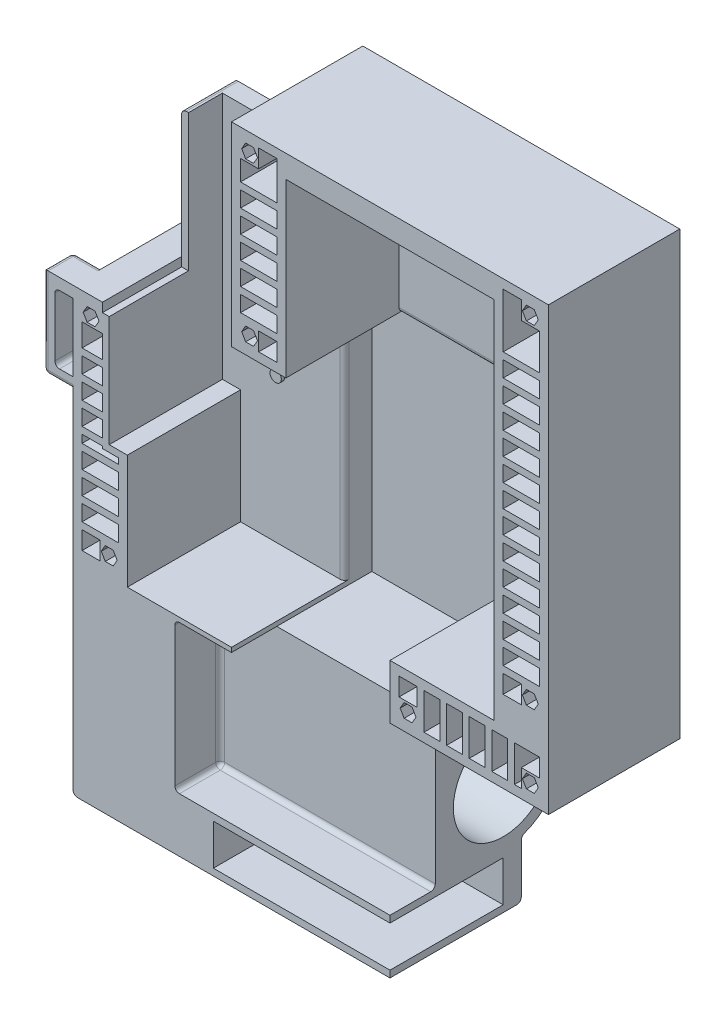
SolidWorks part; units mm, degrees
note: The reader was unsure of these and kept them because the rebuilt part matched: shared geometry of "스케치13<4>", "스케치19<3>", "스케치23<3>".
ref_plane "정면" through (0, 0, 0) normal (0, 0, 1) x (1, 0, 0)
ref_plane "윗면" through (0, 0, 0) normal (0, 1, 0) x (1, 0, 0)
ref_plane "우측면" through (0, 0, 0) normal (1, 0, 0) x (0, 0, -1)
sketch "스케치1" plane through (0, 0, 0) normal (0, 0, 1) x (1, 0, 0)
  line L21 (0, 0) -> (140, 0)
  line L22 (0, 0) -> (0, 195)
  line L23 (0, 195) -> (70, 195)
  line L24 (140, 0) -> (140, 97.5)
  line L25 (140, 97.5) -> (210, 97.5)
  line L26 (70, 195) -> (70, 292.5)
  line L27 (70, 292.5) -> (210, 292.5)
  line L28 (210, 97.5) -> (210, 292.5)
  dimension "D1" = 140
  dimension "D2" = 195
  dimension "D3" = 97.5
  dimension "D4" = 70
  dimension "D5" = 97.5
  dimension "D6" = 70
  dimension "D7" = 195
  dimension "D8" = 140
  dimension "D9" = 140
extrude "보스-돌출1" add sketch "스케치1" along normal blind 8
sketch "스케치6" plane through (0, 0, 8) normal (0, 0, 1) x (1, 0, 0)
  line L0 (140, 0) -> (140, 97.5) construction
  line L1 (0, 0) -> (140, 0)
  line L2 (0, 0) -> (0, 24)
  line L3 (0, 24) -> (140, 24)
  line L4 (140, 0) -> (140, 24)
  line L5 (210, 97.5) -> (210, 292.5) construction
  line L6 (70, 195) -> (94, 195)
  line L7 (70, 195) -> (70, 292.5)
  line L9 (94, 195) -> (94, 282.5)
  line L10 (210, 292.5) -> (70, 292.5) construction
  line L11 (70, 292.5) -> (210, 292.5)
  line L13 (94, 282.5) -> (186, 282.5)
  line L15 (140, 97.5) -> (210, 97.5) construction
  line L17 (210, 292.5) -> (210, 129.5)
  line L18 (210, 97.5) -> (202, 97.5)
  line L19 (186, 282.5) -> (186, 129.5)
  line L20 (210, 121.5) -> (210, 97.5)
  line L21 (210, 97.5) -> (140, 97.5)
  line L23 (186, 121.5) -> (140, 121.5)
  line L24 (140, 97.5) -> (140, 121.5)
  line L25 (0, 195) -> (24, 195)
  line L26 (0, 195) -> (0, 24)
  line L27 (0, 24) -> (24, 24)
  line L28 (24, 195) -> (24, 24)
  line L29 (186, 121.5) -> (210, 121.5)
  line L31 (186, 129.5) -> (210, 129.5)
  line L33 (24, 195) -> (13, 195)
  line L34 (24, 195) -> (24, 139)
  line L35 (24, 139) -> (13, 139)
  line L36 (13, 195) -> (13, 139)
  line M7 (0, 195) -> (0, 0)
  line M8 (0, 0) -> (140, 0)
  line M9 (140, 0) -> (140, 97.5)
  line M10 (140, 97.5) -> (210, 97.5)
  line M11 (210, 97.5) -> (210, 292.5)
  line M12 (210, 292.5) -> (70, 292.5)
  line M13 (70, 292.5) -> (70, 195)
  line M14 (70, 195) -> (0, 195)
  dimension "D1" = 24
  dimension "D2" = 56
  dimension "D3" = 24
  dimension "D4" = 24
  dimension "D5" = 8
  dimension "D6" = 8
  dimension "D7" = 10
  dimension "D8" = 24
  dimension "D9" = 11
  dimension "D10" = 24
extrude "보스-돌출3" add sketch "스케치6" along normal blind 50 contours L28 L27 M14 M7 | L3 M7 M8 M9 | L29 L23 L24 M10 M11 | L19 L31 L6 L9 L13 M11 M12 M13
sketch "스케치8" plane through (0, 0, 0) normal (-1, 0, 0) x (0, 0, 1)
  line L1 (58, 0) -> (0, 0) construction
  circle A0 centre (8, 51) radius 27
  dimension "D1" = 51
  dimension "D2" = 54
extrude "보스-돌출4" add sketch "스케치8" against normal blind 140
sketch "스케치9" plane through (0, 0, 0) normal (-1, 0, 0) x (0, 0, 1)
  circle A0 centre (8, 51) radius 36.5
  dimension "D1" = 73
extrude "컷-돌출1" cut sketch "스케치9" against normal blind 42
ref_plane "평면3" through (0, 0, 38) normal (0, 0, -1) x (-1, 0, 0)
sketch "스케치11" plane through (0, 0, 38) normal (0, 0, -1) x (-1, 0, 0)
  line L0 (-140, 78) -> (-140, 97.5) construction
  line L1 (-42, 24) -> (-140, 24)
  line L2 (-42, 24) -> (-42, 91.5)
  line L3 (-42, 91.5) -> (-140, 91.5)
  line L4 (-140, 24) -> (-140, 91.5)
  dimension "D1" = 67.5
sketch "스케치13" plane through (42, 0, 0) normal (-1, 0, 0) x (0, 0, 1)
  circle A0 centre (8, 51) radius 22
  dimension "D1" = 44
extrude "컷-돌출2" cut sketch "스케치13" against normal blind 80 contours A0
extrude "보스-돌출6" add sketch "스케치11" along normal blind 30
extrude "컷-돌출4" cut sketch "스케치13<4>" against normal blind 80
sketch "스케치13<4>" plane through (42, 0, 0) normal (-1, 0, 0) x (0, 0, 1) same geometry as "스케치13"
sketch "스케치14" plane through (0, 0, 38) normal (0, 0, 1) x (1, 0, 0)
  line L1 (42, 91.5) -> (140, 91.5)
  line L2 (42, 91.5) -> (42, 89.5)
  line L3 (42, 89.5) -> (140, 89.5)
  line L4 (140, 91.5) -> (140, 89.5)
  line L9 (42, 91.5) -> (140, 91.5) construction
  dimension "D2" = 2
extrude "보스-돌출7" add sketch "스케치14" along normal blind 20
sketch "스케치15" plane through (24, 0, 0) normal (1, 0, 0) x (0, 0, -1)
  line L0 (-58, 24) -> (-58, 91.5)
  line L1 (-58, 91.5) -> (-8, 91.5)
  line L2 (-8, 91.5) -> (-8, 87.5)
  line L3 (-8, 139) -> (-8, 87.5) construction
  line L4 (-8, 14.5) -> (-58, 14.5)
  line L5 (-58, 0) -> (-58, 24) construction
  line L6 (-58, 14.5) -> (-58, 24)
  arc A0 (-8, 87.5) -> (-32.5611, 24) centre (-8, 51) ccw construction
  arc A1 (-8, 87.5) -> (-8, 14.5) centre (-8, 51) ccw
  arc A2 (0, 86.6125) -> (0, 15.3875) centre (-8, 51) ccw construction
  arc A3 (-32.5611, 24) -> (0, 15.3875) centre (-8, 51) ccw construction
extrude "보스-돌출9" add sketch "스케치15" along normal up to vertex (18 mm away)
sketch "스케치17" plane through (140, 0, 0) normal (1, 0, 0) x (0, 0, -1)
  line L0 (-58, 0) -> (0, 0) construction
  line L1 (-58, 21) -> (-8, 21)
  line L2 (-58, 21) -> (-58, 3)
  line L3 (-58, 3) -> (-8, 3)
  line L4 (-8, 21) -> (-8, 3)
  line L5 (0, 0) -> (0, 25.2124) construction
  dimension "D1" = 50
  dimension "D2" = 18
  dimension "D3" = 3
  dimension "D4" = 8
extrude "컷-돌출5" cut sketch "스케치17" against normal blind 78
sketch "스케치18" plane through (0, 0, 8) normal (0, 0, 1) x (1, 0, 0)
  line L0 (70, 195) -> (13, 195) construction
  line L1 (16, 91.5) -> (70, 91.5)
  line L2 (16, 91.5) -> (16, 251.5)
  line L3 (16, 251.5) -> (70, 251.5)
  line L4 (70, 91.5) -> (70, 251.5)
  line L5 (24, 91.5) -> (140, 91.5) construction
  line L6 (70, 292.5) -> (70, 195) construction
  dimension "D1" = 56.5
  dimension "D2" = 54
extrude "보스-돌출10" add sketch "스케치18" against normal blind 8
sketch "스케치19" plane through (0, 0, 8) normal (0, 0, 1) x (1, 0, 0)
  line L1 (16, 251.5) -> (13, 251.5)
  line L2 (16, 251.5) -> (16, 139)
  line L3 (16, 139) -> (13, 139)
  line L4 (13, 251.5) -> (13, 139)
  line L5 (24, 139) -> (13, 139) construction
  dimension "D1" = 3
extrude "보스-돌출11" add sketch "스케치19" against normal blind 8
extrude "보스-돌출12" add sketch "스케치19<3>" along normal blind 15
sketch "스케치19<3>" plane through (0, 0, 8) normal (0, 0, 1) x (1, 0, 0) same geometry as "스케치19"
sketch "스케치22" plane through (0, 0, 8) normal (0, 0, 1) x (1, 0, 0)
  line L1 (70, 89.5) -> (140, 89.5)
  line L2 (70, 89.5) -> (70, 206.5)
  line L3 (70, 206.5) -> (140, 206.5)
  line L4 (140, 89.5) -> (140, 206.5)
extrude "보스-돌출14" add sketch "스케치22" along normal mid plane 40 contours L4 L3 L2 L1
sketch "스케치23" plane through (0, 0, 0) normal (0, 0, -1) x (-1, 0, 0)
  line L1 (-140, 206.5) -> (-70, 206.5)
  line L2 (-140, 206.5) -> (-140, 89.5)
  line L3 (-140, 89.5) -> (-70, 89.5)
  line L4 (-70, 206.5) -> (-70, 89.5)
extrude "컷-돌출6" cut sketch "스케치23" against normal through all
extrude "컷-돌출8" cut sketch "스케치23<3>" along normal blind 4
sketch "스케치23<3>" plane through (0, 0, 0) normal (0, 0, -1) x (-1, 0, 0) same geometry as "스케치23"
sketch "스케치26" plane through (0, 0, -12) normal (0, 0, -1) x (-1, 0, 0)
  line L1 (-140, 97.5) -> (-148, 97.5)
  line L2 (-140, 97.5) -> (-140, 206.5)
  line L3 (-140, 206.5) -> (-148, 206.5)
  line L4 (-148, 97.5) -> (-148, 206.5)
  line L5 (-148, 206.5) -> (-62, 206.5)
  line L6 (-148, 206.5) -> (-148, 214.5)
  line L7 (-148, 214.5) -> (-62, 214.5)
  line L8 (-62, 206.5) -> (-62, 214.5)
  line L9 (-62, 206.5) -> (-70, 206.5)
  line L10 (-62, 206.5) -> (-62, 89.5)
  line L11 (-62, 89.5) -> (-70, 89.5)
  line L12 (-70, 206.5) -> (-70, 89.5)
  line L13 (-140, 89.5) -> (-62, 89.5)
  line L14 (-140, 89.5) -> (-140, 81.5)
  line L15 (-140, 81.5) -> (-62, 81.5)
  line L16 (-62, 89.5) -> (-62, 81.5)
  line M10 (-140, 89.5) -> (-70, 89.5)
  line M11 (-70, 89.5) -> (-70, 206.5)
  line M12 (-70, 206.5) -> (-140, 206.5)
  line M13 (-140, 206.5) -> (-140, 89.5)
  dimension "D1" = 8
  dimension "D2" = 8
extrude "보스-돌출16" add sketch "스케치26" against normal blind 12 contours L5 L8 L7 L6 L3 M12 | L11 L10 L5 M11 | L4 L1 L3 M13 | L16 L11 L14 L15 M10
sketch "스케치30" plane through (0, 0, 8) normal (0, 0, 1) x (1, 0, 0)
  line L0 (13, 195) -> (0, 195) construction
  line L1 (6.7273, 195) -> (13.8607, 195)
  line L5 (70, 206.5) -> (94, 206.5) construction
  line L10 (74, 210.5) -> (90, 210.5)
  line L11 (74, 210.5) -> (74, 288.5)
  line L12 (74, 288.5) -> (90, 288.5)
  line L13 (90, 210.5) -> (90, 288.5)
  line L14 (190, 288.5) -> (206, 288.5)
  line L17 (206, 288.5) -> (206, 272.5)
  line L19 (206, 272.5) -> (206, 133.5)
  line L20 (206, 133.5) -> (190, 133.5)
  line L21 (190, 288.5) -> (190, 133.5)
  line L22 (94, 206.5) -> (94, 282.5) construction
  line L23 (70, 292.5) -> (70, 206.5) construction
  line L24 (210, 292.5) -> (70, 292.5) construction
  line L27 (210, 129.5) -> (210, 292.5) construction
  line L28 (186, 129.5) -> (210, 129.5) construction
  line L29 (24, 91.5) -> (70, 91.5) construction
  line L30 (144, 117.5) -> (206, 117.5)
  line L31 (144, 117.5) -> (144, 101.5)
  line L32 (144, 101.5) -> (206, 101.5)
  line L33 (206, 117.5) -> (206, 101.5)
  line L38 (4, 191) -> (20, 191)
  line L39 (4, 191) -> (4, 95.5)
  line L40 (4, 95.5) -> (20, 95.5)
  line L41 (20, 191) -> (20, 95.5)
  line L42 (0, 195) -> (0, 0) construction
  line L43 (24, 139) -> (24, 91.5) construction
  line L47 (210, 97.5) -> (210, 121.5) construction
  line L48 (140, 121.5) -> (210, 121.5) construction
  line L49 (140, 97.5) -> (210, 97.5) construction
  line L50 (140, 97.5) -> (140, 121.5) construction
  point P22 (0, 0)
  point P23 (0, 0)
  point P24 (0, 0)
  point P25 (0, 0)
  point P34 (0, 0)
  point P42 (12, 95.5)
  dimension "D1" = 4
  dimension "D2" = 4
  dimension "D3" = 4
  dimension "D4" = 4
  dimension "D7" = 4
  dimension "D8" = 4
  dimension "D9" = 4
  dimension "D10" = 4
  dimension "D11" = 4
  dimension "D12" = 4
  dimension "D17" = 4
  dimension "D18" = 4
  dimension "D19" = 4
  dimension "D20" = 4
extrude "컷-돌출10" cut sketch "스케치30" along normal through all
sketch "스케치31" plane through (0, 0, 8) normal (0, 0, 1) x (1, 0, 0)
  line L0 (206, 141.5) -> (198, 141.5)
  line L1 (206, 288.5) -> (198, 288.5)
  line L2 (206, 288.5) -> (206, 280.5)
  line L3 (206, 280.5) -> (198, 280.5)
  line L4 (198, 288.5) -> (198, 280.5)
  line L5 (200.25, 287.5322) -> (198.5, 284.5011)
  line L6 (198.5, 284.5011) -> (200.25, 281.47)
  line L7 (200.25, 281.47) -> (203.75, 281.47)
  line L8 (203.75, 281.47) -> (205.5, 284.5011)
  line L9 (205.5, 284.5011) -> (203.75, 287.5322)
  line L10 (203.75, 287.5322) -> (200.25, 287.5322)
  line L11 (206, 141.5) -> (206, 133.5)
  line L12 (206, 133.5) -> (198, 133.5)
  line L13 (198, 141.5) -> (198, 133.5)
  line L20 (206, 109.5) -> (198, 109.5)
  line L21 (206, 109.5) -> (206, 101.5)
  line L22 (206, 101.5) -> (198, 101.5)
  line L23 (198, 109.5) -> (198, 101.5)
  line L30 (152, 109.5) -> (144, 109.5)
  line L31 (152, 109.5) -> (152, 101.5)
  line L32 (152, 101.5) -> (144, 101.5)
  line L33 (144, 109.5) -> (144, 101.5)
  line L40 (82, 218.5) -> (74, 218.5)
  line L41 (82, 218.5) -> (82, 210.5)
  line L42 (82, 210.5) -> (74, 210.5)
  line L43 (74, 218.5) -> (74, 210.5)
  line L50 (82, 288.5) -> (74, 288.5)
  line L51 (82, 288.5) -> (82, 280.5)
  line L52 (82, 280.5) -> (74, 280.5)
  line L53 (74, 288.5) -> (74, 280.5)
  line L54 (76.25, 287.5322) -> (74.5, 284.5011)
  line L55 (74.5, 284.5011) -> (76.25, 281.47)
  line L56 (76.25, 281.47) -> (79.75, 281.47)
  line L57 (79.75, 281.47) -> (81.5, 284.5011)
  line L58 (81.5, 284.5011) -> (79.75, 287.5322)
  line L59 (79.75, 287.5322) -> (76.25, 287.5322)
  line L60 (12, 191) -> (4, 191)
  line L61 (12, 191) -> (12, 183)
  line L62 (12, 183) -> (4, 183)
  line L63 (4, 191) -> (4, 183)
  line L64 (6.25, 189.9877) -> (4.5, 186.9566)
  line L65 (4.5, 186.9566) -> (6.2243, 183.97)
  line L66 (6.2243, 183.97) -> (9.7757, 183.97)
  line L67 (9.7757, 183.97) -> (11.5, 186.9566)
  line L68 (11.5, 186.9566) -> (9.75, 189.9877)
  line L69 (9.75, 189.9877) -> (6.25, 189.9877)
  line L70 (20, 103.5) -> (12, 103.5)
  line L71 (20, 103.5) -> (20, 95.5)
  line L72 (20, 95.5) -> (12, 95.5)
  line L73 (12, 103.5) -> (12, 95.5)
  line L80 (74, 288.5) -> (90, 288.5) construction
  line L81 (74, 210.5) -> (74, 288.5) construction
  line L82 (74, 210.5) -> (90, 210.5) construction
  line L83 (206, 288.5) -> (206, 133.5) construction
  line L84 (76.25, 217.5322) -> (74.5, 214.5011)
  line L85 (74.5, 214.5011) -> (76.25, 211.47)
  line L86 (76.25, 211.47) -> (79.75, 211.47)
  line L87 (79.75, 211.47) -> (81.5, 214.5011)
  line L88 (81.5, 214.5011) -> (79.75, 217.5322)
  line L89 (79.75, 217.5322) -> (76.25, 217.5322)
  line L90 (206, 133.5) -> (190, 133.5) construction
  line L91 (206, 117.5) -> (206, 101.5) construction
  line L92 (200.25, 140.5322) -> (198.5, 137.5011)
  line L93 (198.5, 137.5011) -> (200.25, 134.47)
  line L94 (200.25, 134.47) -> (203.75, 134.47)
  line L95 (203.75, 134.47) -> (205.5, 137.5011)
  line L96 (205.5, 137.5011) -> (203.75, 140.5322)
  line L97 (203.75, 140.5322) -> (200.25, 140.5322)
  line L98 (144, 101.5) -> (206, 101.5) construction
  line L99 (144, 117.5) -> (144, 101.5) construction
  line L100 (200.25, 108.5322) -> (198.5, 105.5011)
  line L101 (198.5, 105.5011) -> (200.25, 102.47)
  line L102 (200.25, 102.47) -> (203.75, 102.47)
  line L103 (203.75, 102.47) -> (205.5, 105.5011)
  line L104 (205.5, 105.5011) -> (203.75, 108.5322)
  line L105 (203.75, 108.5322) -> (200.25, 108.5322)
  line L112 (4, 191) -> (13, 191) construction
  line L113 (144.5, 105.5011) -> (146.25, 102.47)
  line L114 (146.25, 102.47) -> (149.75, 102.47)
  line L115 (149.75, 102.47) -> (151.5, 105.5011)
  line L116 (151.5, 105.5011) -> (149.75, 108.5322)
  line L117 (149.75, 108.5322) -> (146.25, 108.5322)
  line L118 (146.25, 108.5322) -> (144.5, 105.5011)
  line L119 (4, 95.5) -> (20, 95.5) construction
  line L120 (20, 139) -> (20, 95.5) construction
  line L121 (4, 191) -> (4, 95.5) construction
  line L123 (14.25, 102.5322) -> (12.5, 99.5011)
  line L124 (12.5, 99.5011) -> (14.25, 96.47)
  line L125 (14.25, 96.47) -> (17.75, 96.47)
  line L126 (17.75, 96.47) -> (19.5, 99.5011)
  line L127 (19.5, 99.5011) -> (17.75, 102.5322)
  line L128 (17.75, 102.5322) -> (14.25, 102.5322)
  circle A0 centre (202, 284.5011) radius 3.5 construction
  circle A5 centre (78, 284.5011) radius 3.5 construction
  circle A6 centre (8, 186.9566) radius 3.5 construction
  circle A8 centre (78, 214.5011) radius 3.5 construction
  circle A9 centre (202, 137.5011) radius 3.5 construction
  circle A10 centre (202, 105.5011) radius 3.5 construction
  circle A11 centre (148, 105.5011) radius 3.5 construction
  circle A12 centre (16, 99.5011) radius 3.5 construction
  point P6 (202, 288.5)
  point P71 (78, 288.5)
  point P84 (8, 191)
  dimension "D3" = 7
  dimension "D9" = 7
  dimension "D15" = 0.97
  dimension "D21" = 0.5
  dimension "D27" = 7
  dimension "D33" = 7
  dimension "D39" = 7
  dimension "D12" = 7
  dimension "D17" = 7
  dimension "D22" = 7
  dimension "D1" = 8
  dimension "D2" = 8
  dimension "D4" = 0.5
  dimension "D5" = 0.97
  dimension "D6" = 0.9678
  dimension "D7" = 8
  dimension "D8" = 8
  dimension "D10" = 0.97
  dimension "D11" = 0.5
  dimension "D13" = 8
  dimension "D14" = 8
  dimension "D16" = 0.5
  dimension "D18" = 0.97
  dimension "D19" = 8
  dimension "D20" = 8
  dimension "D23" = 0.97
  dimension "D24" = 0.5
  dimension "D25" = 8
  dimension "D26" = 8
  dimension "D28" = 0.97
  dimension "D29" = 0.5
  dimension "D31" = 8
  dimension "D32" = 8
  dimension "D34" = 0.5
  dimension "D35" = 0.97
  dimension "D36" = 0.9678
  dimension "D37" = 8
  dimension "D38" = 8
  dimension "D40" = 0.5
  dimension "D41" = 0.97
  dimension "D42" = 1.0123
  dimension "D43" = 8
  dimension "D44" = 8
extrude "보스-돌출17" add sketch "스케치31" along normal blind 50
sketch "스케치32" plane through (0, 0, 8) normal (0, 0, 1) x (1, 0, 0)
  line L0 (12, 191) -> (13, 191) construction
  line L1 (4.0007, 183) -> (12.0007, 183)
  line L2 (4.0007, 183) -> (4.0007, 191)
  line L3 (4.0007, 191) -> (12.0007, 191)
  line L4 (12.0007, 183) -> (12.0007, 191)
  line L5 (12, 103.5) -> (20, 103.5)
  line L6 (12, 103.5) -> (12, 95.5)
  line L7 (12, 95.5) -> (20, 95.5)
  line L8 (20, 103.5) -> (20, 95.5)
  line L9 (152, 109.5) -> (144, 109.5)
  line L10 (152, 109.5) -> (152, 101.5)
  line L11 (152, 101.5) -> (144, 101.5)
  line L12 (144, 109.5) -> (144, 101.5)
  line L13 (198, 109.5) -> (206, 109.5)
  line L14 (198, 109.5) -> (198, 101.5)
  line L15 (198, 101.5) -> (206, 101.5)
  line L16 (206, 109.5) -> (206, 101.5)
  line L17 (198, 141.5) -> (206, 141.5)
  line L18 (198, 141.5) -> (198, 133.5)
  line L19 (198, 133.5) -> (206, 133.5)
  line L20 (206, 141.5) -> (206, 133.5)
  line L21 (198, 280.5) -> (206, 280.5)
  line L22 (198, 280.5) -> (198, 288.5)
  line L23 (198, 288.5) -> (206, 288.5)
  line L24 (206, 280.5) -> (206, 288.5)
  line L25 (82, 280.5) -> (74, 280.5)
  line L26 (82, 280.5) -> (82, 288.5)
  line L27 (82, 288.5) -> (74, 288.5)
  line L28 (74, 280.5) -> (74, 288.5)
  line L29 (82, 218.5) -> (74, 218.5)
  line L30 (82, 218.5) -> (82, 210.5)
  line L31 (82, 210.5) -> (74, 210.5)
  line L32 (74, 218.5) -> (74, 210.5)
  dimension "D1" = 8
  dimension "D2" = 8
  dimension "D3" = 8
  dimension "D4" = 8
  dimension "D5" = 8
  dimension "D6" = 8
  dimension "D7" = 8
  dimension "D8" = 8
  dimension "D9" = 8
  dimension "D10" = 8
  dimension "D11" = 8
  dimension "D12" = 8
  dimension "D13" = 8
  dimension "D14" = 8
  dimension "D15" = 8
  dimension "D16" = 8
extrude "보스-돌출18" add sketch "스케치32" along normal blind 7
sketch "스케치33" plane through (122, 0, 0) normal (-1, 0, 0) x (0, 0, 1)
  circle A0 centre (8, 51) radius 22
extrude "컷-돌출11" cut sketch "스케치33" against normal through all
sketch "스케치34" plane through (0, 0, 0) normal (0, 0, -1) x (-1, 0, 0)
  line L5 (-42, 76.7876) -> (-140, 76.7876) construction
  line L6 (-140, 81.5) -> (-55.849, 81.5)
  line L7 (-140, 81.5) -> (-140, 76.7876)
  line L8 (-140, 76.7876) -> (-55.849, 76.7876)
  line L9 (-55.849, 81.5) -> (-55.849, 76.7876)
  line L10 (-148, 97.5) -> (-152.71, 97.5)
  line L11 (-62, 214.5) -> (-57.29, 214.5)
  line L12 (-62, 214.5) -> (-62, 81.5)
  line L13 (-62, 81.5) -> (-57.29, 81.5)
  line L14 (-57.29, 214.5) -> (-57.29, 81.5)
  line L19 (-148, 214.5) -> (-57.29, 214.5)
  line L20 (-148, 214.5) -> (-148, 219.21)
  line L21 (-148, 219.21) -> (-57.29, 219.21)
  line L22 (-57.29, 214.5) -> (-57.29, 219.21)
  line L23 (-148, 97.5) -> (-148, 219.21)
  line L24 (-148, 219.21) -> (-152.71, 219.21)
  line L25 (-152.71, 97.5) -> (-152.71, 219.21)
  line M16 (-148, 214.5) -> (-62, 214.5)
  line M17 (-62, 214.5) -> (-62, 81.5)
  dimension "D1" = 4.7124
  dimension "D2" = 4.71
  dimension "D3" = 4.71
  dimension "D4" = 4.71
extrude "보스-돌출19" add sketch "스케치34" along normal up to vertex (12 mm away) contours L14 L11 L6 M17 | L11 L22 L21 L20 M16 | L25 L24 L23 L10
sketch "스케치35" plane through (42, 0, 0) normal (-1, 0, 0) x (0, 0, 1)
  line L0 (13.9526, 72.1794) -> (13.9526, 60)
  line L1 (13.9526, 42) -> (13.9526, 29.8206)
  line L2 (8, 60) -> (13.9526, 60)
  line L4 (8, 42) -> (13.9526, 42)
  arc A0 (13.9526, 72.1794) -> (13.9526, 29.8206) centre (8, 51) ccw
  circle A1 centre (8, 65) radius 1.5
  circle A2 centre (8, 37) radius 1.5
  arc A3 (8, 60) -> (8, 42) centre (8, 51) ccw
  dimension "D1" = 3
  dimension "D2" = 3
  dimension "D6" = 18
  dimension "D3" = 28
  dimension "D4" = 14
  dimension "D5" = 14
extrude "보스-돌출20" add sketch "스케치35" against normal blind 8
sketch "스케치38" plane through (0, 89.5, 0) normal (0, 1, 0) x (1, 0, 0)
  line L1 (129.6616, -21.5) -> (112.0139, -21.5)
  line L2 (129.6616, -21.5) -> (129.6616, -1.5)
  line L3 (129.6616, -1.5) -> (112.0139, -1.5)
  line L4 (112.0139, -21.5) -> (112.0139, -1.5)
  line L5 (140, 4) -> (70, 4) construction
  dimension "D1" = 5.5
  dimension "D2" = 20
extrude "컷-돌출12" cut sketch "스케치38" against normal blind 36
sketch "스케치39" plane through (0, 3, 0) normal (0, 1, 0) x (1, 0, 0)
  line L0 (80.5, -33) -> (86.5, -33) construction
  line L1 (80.5, -30.5) -> (86.5, -30.5)
  line L2 (80.5, -35.5) -> (86.5, -35.5)
  line L3 (97.5, -36) -> (97.5, -30) construction
  line L4 (95, -36) -> (95, -30)
  line L5 (100, -36) -> (100, -30)
  line L6 (62, -58) -> (62, -8) construction
  line L7 (62, -58) -> (140, -58) construction
  arc A0 (80.5, -30.5) -> (80.5, -35.5) centre (80.5, -33) ccw
  arc A1 (86.5, -35.5) -> (86.5, -30.5) centre (86.5, -33) ccw
  arc A2 (95, -36) -> (100, -36) centre (97.5, -36) ccw
  arc A3 (100, -30) -> (95, -30) centre (97.5, -30) ccw
  circle A4 centre (107, -33) radius 2.5
  point P2 (83.5, -33)
  point P7 (97.5, -33)
  dimension "D5" = 5
  dimension "D1" = 6
  dimension "D2" = 6
  dimension "D3" = 5
  dimension "D4" = 5
  dimension "D6" = 9.5
  dimension "D7" = 11
  dimension "D8" = 18.5
  dimension "D9" = 25
extrude "보스-돌출21" add sketch "스케치39" along normal blind 5
sketch "스케치40" plane through (0, 0, 0) normal (-1, 0, 0) x (0, 0, 1)
  line L0 (58, 195) -> (58, 0) construction
  line L1 (58, 195) -> (45, 195)
  line L2 (58, 195) -> (58, 190)
  line L3 (58, 190) -> (45, 190)
  line L4 (45, 195) -> (45, 190)
  line L5 (58, 160) -> (45, 160)
  line L6 (58, 160) -> (58, 155)
  line L7 (58, 155) -> (45, 155)
  line L8 (45, 160) -> (45, 155)
  dimension "D1" = 13
  dimension "D2" = 30
extrude "보스-돌출22" add sketch "스케치40" along normal blind 8
sketch "스케치41" plane through (-8, 0, 0) normal (-1, 0, 0) x (0, 0, 1)
  line L0 (45, 155) -> (58, 155) construction
  line L1 (45, 195) -> (58, 195)
  line L2 (45, 195) -> (45, 155)
  line L3 (45, 155) -> (58, 155)
  line L4 (58, 195) -> (58, 155)
  line L5 (45, 155) -> (58, 155) construction
extrude "보스-돌출23" add sketch "스케치41" along normal blind 5
sketch "스케치42" plane through (0, 0, 8) normal (0, 0, 1) x (1, 0, 0)
  line L0 (70, 251.5) -> (16, 251.5) construction
  line L7 (70, 91.5) -> (70, 206.5) construction
  line L8 (16, 191) -> (16, 251.5) construction
  circle B0 centre (41, 156.5) radius 2.5
  circle B1 centre (41, 191) radius 3.5
  line B2 (38.5, 171.5) -> (38.5, 177.5)
  arc B3 (43.5, 177.5) -> (38.5, 177.5) centre (41, 177.5) ccw
  line B4 (43.5, 171.5) -> (43.5, 177.5)
  arc B5 (38.5, 171.5) -> (43.5, 171.5) centre (41, 171.5) ccw
  dimension "D3" = 25
  dimension "D1" = 60.5
  dimension "D2" = 29
sketch_block_instance "블록1-1"
sketch_block "블록1" parameters "D1"=5, "D2"=7, "D3"=5, "D4"=6, "D5"=15, "D6"=13.5
extrude "보스-돌출24" add sketch "스케치42" along normal blind 1.5
sketch "스케치44" plane through (0, 0, 8) normal (0, 0, 1) x (1, 0, 0)
  line L0 (16, 191) -> (16, 251.5) construction
  line L1 (13, 195) -> (16, 195)
  line L2 (13, 195) -> (13, 139)
  line L3 (13, 139) -> (16, 139)
  line L4 (16, 195) -> (16, 139)
  line L5 (24, 139) -> (20, 139) construction
  line L6 (24, 139) -> (24, 91.5) construction
  line L7 (16, 139) -> (24, 139)
  line L8 (16, 139) -> (16, 142)
  line L9 (16, 142) -> (24, 142)
  line L10 (24, 139) -> (24, 142)
  line L12 (12.0007, 183) -> (13, 183)
  line L13 (12.0007, 183) -> (12.0007, 191)
  line L14 (12.0007, 191) -> (13, 191)
  line L15 (13, 183) -> (13, 191)
  line M11 (12.0007, 191) -> (12.0007, 183)
  line M18 (20, 139) -> (24, 139)
  line M25 (16, 191) -> (12.0007, 191)
  dimension "D1" = 3
  dimension "D2" = 3
extrude "보스-돌출27" add sketch "스케치44" along normal blind 50 contours L4 L2 L3 M25 | L12 L2 M11 M25 | L10 L9 L4 L7 M18
sketch "스케치46" plane through (0, 0, 8) normal (0, 0, 1) x (1, 0, 0)
  line L0 (140, 121.5) -> (210, 121.5) construction
  line L1 (210, 129.5) -> (186, 129.5)
  line L2 (210, 129.5) -> (210, 121.5)
  line L3 (210, 121.5) -> (186, 121.5)
  line L4 (186, 129.5) -> (186, 121.5)
  line L5 (186, 282.5) -> (186, 129.5) construction
extrude "보스-돌출28" add sketch "스케치46" along normal blind 50
sketch "스케치47" plane through (0, 0, 38) normal (0, 0, 1) x (1, 0, 0)
  line L0 (42, 89.5) -> (70, 89.5) construction
  line L1 (42, 24) -> (45, 24)
  line L2 (42, 24) -> (42, 89.5)
  line L3 (42, 89.5) -> (45, 89.5)
  line L4 (45, 24) -> (45, 89.5)
  dimension "D1" = 3
extrude "보스-돌출29" add sketch "스케치47" along normal up to vertex (20 mm away)
sketch "스케치48" plane through (0, 0, 8) normal (0, 0, 1) x (1, 0, 0)
  line L0 (144, 117.5) -> (206, 117.5) construction
  line L1 (152, 117.5) -> (155, 117.5)
  line L2 (152, 117.5) -> (152, 101.5)
  line L3 (152, 101.5) -> (155, 101.5)
  line L4 (155, 117.5) -> (155, 101.5)
  line L5 (152, 101.5) -> (198, 101.5) construction
  line L6 (152, 101.5) -> (152, 109.5) construction
  line L11 (162, 117.5) -> (162, 101.5)
  line L12 (162, 117.5) -> (165, 117.5)
  line L13 (165, 117.5) -> (165, 101.5)
  line L14 (162, 101.5) -> (165, 101.5)
  line L15 (172, 117.5) -> (172, 101.5)
  line L16 (172, 117.5) -> (175, 117.5)
  line L17 (175, 117.5) -> (175, 101.5)
  line L18 (172, 101.5) -> (175, 101.5)
  line L19 (182, 117.5) -> (182, 101.5)
  line L20 (182, 117.5) -> (185, 117.5)
  line L21 (185, 117.5) -> (185, 101.5)
  line L22 (182, 101.5) -> (185, 101.5)
  line L23 (192, 117.5) -> (192, 101.5)
  line L24 (192, 117.5) -> (195, 117.5)
  line L25 (195, 117.5) -> (195, 101.5)
  line L26 (192, 101.5) -> (195, 101.5)
  line L27 (190, 288.5) -> (190, 133.5) construction
  line L28 (190, 141.5) -> (206, 141.5)
  line L29 (190, 141.5) -> (190, 144.5)
  line L30 (190, 144.5) -> (206, 144.5)
  line L31 (206, 141.5) -> (206, 144.5)
  line L32 (206, 280.5) -> (206, 141.5) construction
  line L33 (190, 151.5) -> (190, 154.5)
  line L34 (190, 151.5) -> (206, 151.5)
  line L35 (206, 151.5) -> (206, 154.5)
  line L36 (190, 154.5) -> (206, 154.5)
  line L37 (190, 161.5) -> (190, 164.5)
  line L38 (190, 161.5) -> (206, 161.5)
  line L39 (206, 161.5) -> (206, 164.5)
  line L40 (190, 164.5) -> (206, 164.5)
  line L41 (190, 171.5) -> (190, 174.5)
  line L42 (190, 171.5) -> (206, 171.5)
  line L43 (206, 171.5) -> (206, 174.5)
  line L44 (190, 174.5) -> (206, 174.5)
  line L45 (190, 181.5) -> (190, 184.5)
  line L46 (190, 181.5) -> (206, 181.5)
  line L47 (206, 181.5) -> (206, 184.5)
  line L48 (190, 184.5) -> (206, 184.5)
  line L49 (190, 191.5) -> (190, 194.5)
  line L50 (190, 191.5) -> (206, 191.5)
  line L51 (206, 191.5) -> (206, 194.5)
  line L52 (190, 194.5) -> (206, 194.5)
  line L53 (190, 201.5) -> (190, 204.5)
  line L54 (190, 201.5) -> (206, 201.5)
  line L55 (206, 201.5) -> (206, 204.5)
  line L56 (190, 204.5) -> (206, 204.5)
  line L57 (190, 211.5) -> (190, 214.5)
  line L58 (190, 211.5) -> (206, 211.5)
  line L59 (206, 211.5) -> (206, 214.5)
  line L60 (190, 214.5) -> (206, 214.5)
  line L61 (190, 221.5) -> (190, 224.5)
  line L62 (190, 221.5) -> (206, 221.5)
  line L63 (206, 221.5) -> (206, 224.5)
  line L64 (190, 224.5) -> (206, 224.5)
  line L65 (190, 231.5) -> (190, 234.5)
  line L66 (190, 231.5) -> (206, 231.5)
  line L67 (206, 231.5) -> (206, 234.5)
  line L68 (190, 234.5) -> (206, 234.5)
  line L69 (190, 241.5) -> (190, 244.5)
  line L70 (190, 241.5) -> (206, 241.5)
  line L71 (206, 241.5) -> (206, 244.5)
  line L72 (190, 244.5) -> (206, 244.5)
  line L73 (190, 251.5) -> (190, 254.5)
  line L74 (190, 251.5) -> (206, 251.5)
  line L75 (206, 251.5) -> (206, 254.5)
  line L76 (190, 254.5) -> (206, 254.5)
  line L77 (190, 261.5) -> (190, 264.5)
  line L78 (190, 261.5) -> (206, 261.5)
  line L79 (206, 261.5) -> (206, 264.5)
  line L80 (190, 264.5) -> (206, 264.5)
  line L87 (74, 218.5) -> (90, 218.5)
  line L88 (74, 218.5) -> (74, 221.5)
  line L89 (74, 221.5) -> (90, 221.5)
  line L90 (90, 218.5) -> (90, 221.5)
  line L91 (74, 228.5) -> (74, 231.5)
  line L92 (74, 228.5) -> (90, 228.5)
  line L93 (90, 228.5) -> (90, 231.5)
  line L94 (74, 231.5) -> (90, 231.5)
  line L95 (74, 238.5) -> (74, 241.5)
  line L96 (74, 238.5) -> (90, 238.5)
  line L97 (90, 238.5) -> (90, 241.5)
  line L98 (74, 241.5) -> (90, 241.5)
  line L99 (74, 248.5) -> (74, 251.5)
  line L100 (74, 248.5) -> (90, 248.5)
  line L101 (90, 248.5) -> (90, 251.5)
  line L102 (74, 251.5) -> (90, 251.5)
  line L103 (74, 258.5) -> (74, 261.5)
  line L104 (74, 258.5) -> (90, 258.5)
  line L105 (90, 258.5) -> (90, 261.5)
  line L106 (74, 261.5) -> (90, 261.5)
  line L107 (74, 268.5) -> (74, 271.5)
  line L108 (74, 268.5) -> (90, 268.5)
  line L109 (90, 268.5) -> (90, 271.5)
  line L110 (74, 271.5) -> (90, 271.5)
  line L138 (4, 183) -> (4, 95.5) construction
  line L139 (20, 103.5) -> (4, 103.5)
  line L140 (20, 103.5) -> (20, 106.5)
  line L141 (20, 106.5) -> (4, 106.5)
  line L142 (4, 103.5) -> (4, 106.5)
  line L143 (13, 170) -> (4, 170)
  line L144 (13, 170) -> (13, 173)
  line L145 (13, 173) -> (4, 173)
  line L146 (4, 170) -> (4, 173)
  line L147 (13, 183) -> (13, 139) construction
  line L149 (4, 183) -> (12, 183) construction
  line L150 (13, 160) -> (4, 160)
  line L151 (4, 160) -> (4, 163)
  line L152 (13, 163) -> (4, 163)
  line L153 (13, 160) -> (13, 163)
  line L154 (13, 150) -> (4, 150)
  line L155 (4, 150) -> (4, 153)
  line L156 (13, 153) -> (4, 153)
  line L157 (13, 150) -> (13, 153)
  line L158 (13, 140) -> (4, 140)
  line L159 (4, 140) -> (4, 143)
  line L160 (13, 143) -> (4, 143)
  line L161 (13, 140) -> (13, 143)
  line L162 (20, 113.5) -> (20, 116.5)
  line L163 (20, 113.5) -> (4, 113.5)
  line L164 (4, 113.5) -> (4, 116.5)
  line L165 (20, 116.5) -> (4, 116.5)
  line L166 (20, 123.5) -> (20, 126.5)
  line L167 (20, 123.5) -> (4, 123.5)
  line L168 (4, 123.5) -> (4, 126.5)
  line L169 (20, 126.5) -> (4, 126.5)
  line L170 (20, 133.5) -> (20, 136.5)
  line L171 (20, 133.5) -> (4, 133.5)
  line L172 (4, 133.5) -> (4, 136.5)
  line L173 (20, 136.5) -> (4, 136.5)
  dimension "D1" = 3
  dimension "D2" = 5
  dimension "D3" = 3
  dimension "D4" = 13
  dimension "D6" = 3
  dimension "D7" = 6
  dimension "D9" = 3
  dimension "D10" = 3
  dimension "D11" = 10
  dimension "D12" = 4
  dimension "D13" = 4
extrude "보스-돌출30" add sketch "스케치48" along normal up to vertex (50 mm away)
fillet "필렛2" radius 2 12 edges at (-8, 160, 51.5) (-8, 190, 51.5) (-6.5, 155, 45) (-6.5, 155, 58) (-13, 175, 58) (-13, 175, 45) (-13, 155, 51.5) (-13, 195, 51.5) (0, 0, 29) (70, 0, 0) (0, 7.6938, 0) (-6.5, 195, 45)
fillet "필렛3" radius 2 6 edges at (91, 25.2124, 0) (57.29, 150.355, 0) (56.5695, 81.5, 0) (55.849, 79.1438, 0) (152.71, 158.355, 0) (105, 219.21, 0)
fillet "필렛4" radius 2 4 edges at (70, 149, 8) (140, 164, 8) (117, 206.5, 8) (13, 251.5, 11.5)
fillet "필렛5" radius 2 4 edges at (92.5, 24, 38) (45, 24, 48) (45, 56.75, 38) (45, 89.5, 48)
